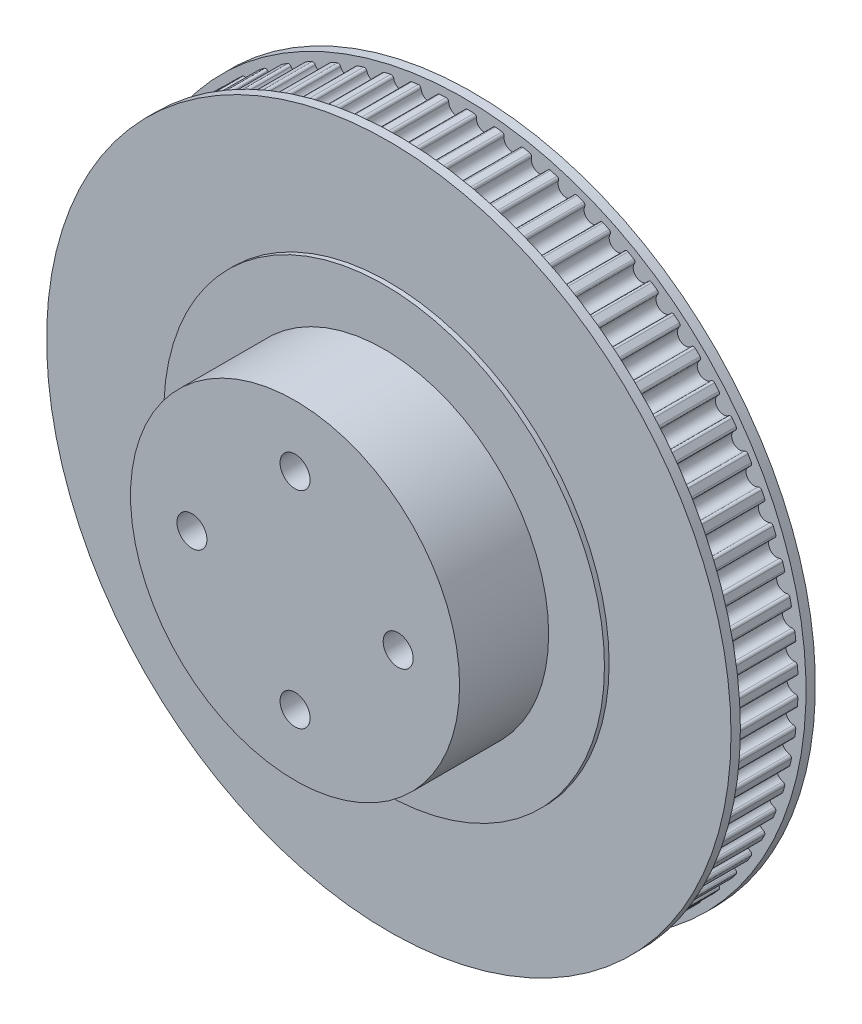
SolidWorks part; units mm, degrees
ref_plane "Front Plane" through (0, 0, 0) normal (1, 0, 0) x (0, 1, 0)
ref_plane "Top Plane" through (0, 0, 0) normal (0, 0, 1) x (0, 1, 0)
ref_plane "Right Plane" through (0, 0, 0) normal (0, 1, 0) x (-1, 0, 0)
sketch "Sketch1" plane through (0, 0, 0) normal (0, 0, 1) x (0, 1, 0)
  line L0 (0, 0) -> (0, 35.6449)
  line L1 (0, 0) -> (2.9827, 35.5199)
  line L2 (0, 0) -> (1.4801, 35.3139) construction
  arc A0 (0.6729, 35.6385) -> (2.3116, 35.5698) centre (1.4801, 35.3139) ccw
  arc A1 (0, 35.6449) -> (0.6729, 35.6385) centre (0, 0) cw
  arc A2 (2.3116, 35.5698) -> (2.9827, 35.5199) centre (0, 0) cw
  dimension "D6" = 1.74
  dimension "D1" = 35.6449
  dimension "D2" = 4.8
  dimension "D3" = 35.6449
  dimension "D4" = 35.3449
  dimension "D5" = 2.4
extrude "Boss-Extrude1" add sketch "Sketch1" along normal blind 7 contours A2 A0 L2 L1 | A1 L0 L2 A0 region at (-23.3406, 1.48, 0) region at (-23.3826, 0.4783, 0)
fillet "Fillet1" radius 0.26 2 edges at (-35.5698, 2.3116, 3.5) (-35.6385, 0.6729, 3.5)
pattern_circular "CirPattern1" count 75 over 360 about axis through (0, 0, 7) along (0, 0, -1) of "Boss-Extrude1", "Fillet1"
sketch "Sketch2" plane through (0, 0, 0) normal (0, 0, -1) x (1, 0, 0)
  circle A0 centre (0, 0) radius 36.5
  dimension "D1" = 73
extrude "Boss-Extrude2" add sketch "Sketch2" along normal blind 1
extrude "Boss-Extrude3" add sketch "Sketch2<2>" against normal blind 1 from surface starting at face at (0, 0, 7)
sketch "Sketch2<2>" plane through (0, 0, 0) normal (0, 0, -1) x (1, 0, 0) same geometry as "Sketch2"
sketch "Sketch4" plane through (0, 0, 8) normal (0, 0, 1) x (1, 0, 0)
  circle A0 centre (0, 0) radius 17.55
  circle A1 centre (0, 0) radius 23.5
  dimension "D1" = 35.1
  dimension "D2" = 47
extrude "Boss-Extrude4" add sketch "Sketch4" along normal blind 0.5 contours A1
extrude "Boss-Extrude5" add sketch "Sketch4<3>" along normal blind 9.5 from surface contours A0 region at (0, 0, 8) starting at face at (23.5, 0, 8.5)
sketch "Sketch4<3>" plane through (0, 0, 8) normal (0, 0, 1) x (1, 0, 0) same geometry as "Sketch4"
sketch "Sketch3" plane through (0, 0, -1) normal (0, 0, -1) x (1, 0, 0)
  line L0 (13.75, -2.75) -> (8.25, -2.75)
  line L1 (-2.75, 13.75) -> (2.75, 13.75)
  line L2 (-2.75, 13.75) -> (-2.75, 8.25)
  line L3 (-2.75, 8.25) -> (2.75, 8.25)
  line L4 (2.75, 13.75) -> (2.75, 8.25)
  line L5 (-2.75, 13.75) -> (2.75, 8.25) construction
  line L6 (-2.75, 8.25) -> (2.75, 13.75) construction
  line L7 (8.25, 2.75) -> (8.25, -2.75)
  line L8 (13.75, 2.75) -> (8.25, 2.75)
  line L9 (13.75, 2.75) -> (13.75, -2.75)
  line L10 (-2.75, -13.75) -> (-2.75, -8.25)
  line L11 (2.75, -8.25) -> (-2.75, -8.25)
  line L12 (2.75, -13.75) -> (2.75, -8.25)
  line L13 (2.75, -13.75) -> (-2.75, -13.75)
  line L14 (-13.75, 2.75) -> (-8.25, 2.75)
  line L15 (-8.25, -2.75) -> (-8.25, 2.75)
  line L16 (-13.75, -2.75) -> (-8.25, -2.75)
  line L17 (-13.75, -2.75) -> (-13.75, 2.75)
  circle A0 centre (0, 0) radius 11 construction
  circle A1 centre (0, 11) radius 1.6
  circle A2 centre (11, 0) radius 1.6
  circle A3 centre (0, -11) radius 1.6
  circle A4 centre (-11, 0) radius 1.6
  point P30 (0, 0)
  dimension "D1" = 22
  dimension "D2" = 4
  dimension "3.2" = 3.2
extrude "Cut-Extrude1" cut sketch "Sketch3" against normal blind 19 contours A1 | A4 | A2 | A3
extrude "Cut-Extrude2" cut sketch "Sketch3<3>" against normal blind 7
sketch "Sketch3<3>" plane through (0, 0, -1) normal (0, 0, -1) x (1, 0, 0) same geometry as "Sketch3"
equation "\"D1@Sketch1\"=3 * 75 / PI / 2 - 0.165"
equation "\"D2@Sketch1\"=360 / 75"
equation "\"D3@Sketch1\"=\"D1@Sketch1\""
equation "\"D4@Sketch1\"=\"D1@Sketch1\"-1.17+1.74/2"
